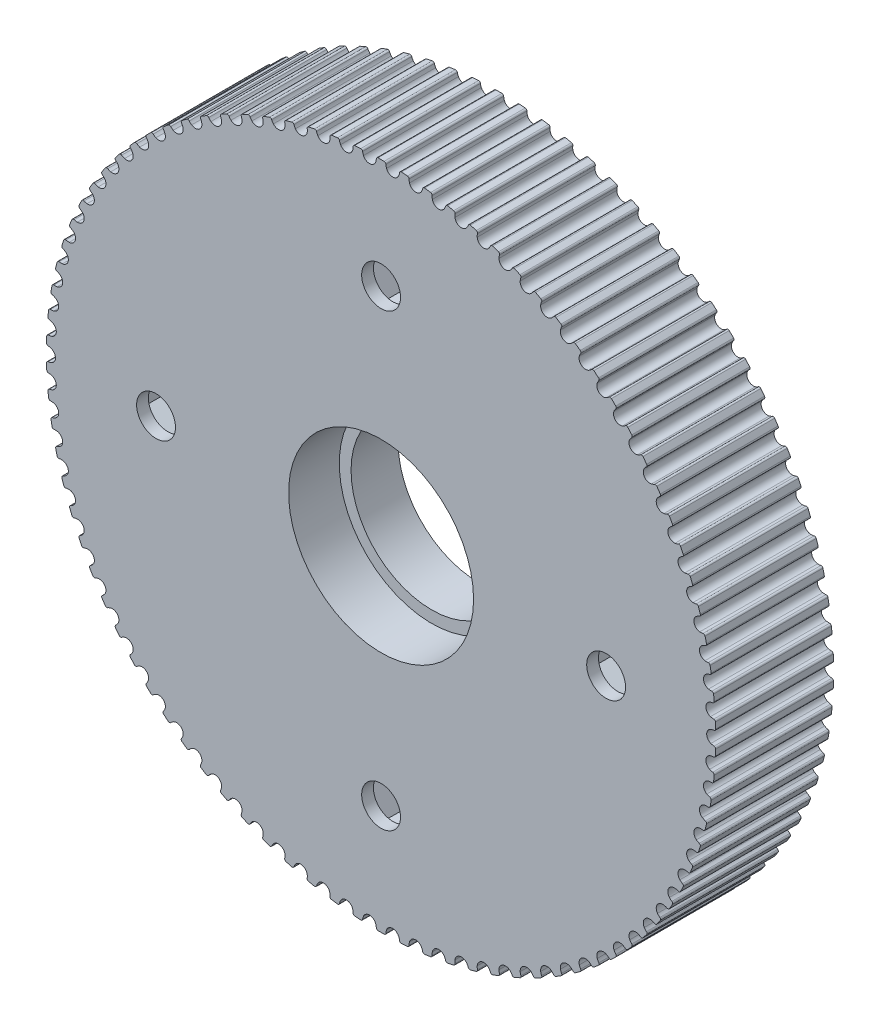
SolidWorks part; units mm, degrees
ref_plane "前视基准面" through (0, 0, 0) normal (0, 0, 1) x (1, 0, 0)
ref_plane "上视基准面" through (0, 0, 0) normal (0, 1, 0) x (1, 0, 0)
ref_plane "右视基准面" through (0, 0, 0) normal (1, 0, 0) x (0, 0, -1)
sketch "草图5" plane through (0, 0, 0) normal (0, 0, 1) x (1, 0, 0)
  line L0 (-10.0057, 26.1448) -> (-10.0057, 26.1386)
  line L1 (-10.0057, -26.1386) -> (-10.0057, -26.1448)
  arc A0 (-8.1576, 26.7791) -> (-8.1799, 27.0557) centre (-9.1558, 26.8376) ccw
  arc A1 (-9.1407, 26.4596) -> (-8.1576, 26.7791) centre (-8.7116, 26.8116) ccw
  arc A2 (-9.2853, 26.6965) -> (-9.1407, 26.4596) centre (-8.3675, 27.0938) ccw
  arc A3 (-9.2853, 26.6965) -> (-9.4729, 26.7784) centre (-9.4229, 26.637) ccw
  arc A4 (-9.4729, 26.7784) -> (-9.9561, 26.6025) centre (-0.0036, 0.01) ccw
  arc A5 (-9.9561, 26.6025) -> (-10.0473, 26.4192) centre (-9.9035, 26.462) ccw
  arc A6 (-10.0057, 26.1448) -> (-10.0473, 26.4192) centre (-11.0056, 26.1336) ccw
  arc A7 (-10.9642, 25.7576) -> (-10.0057, 26.1386) centre (-10.5607, 26.1386) ccw
  arc A8 (-11.1249, 25.9838) -> (-10.9642, 25.7576) centre (-10.2371, 26.4441) ccw
  arc A9 (-11.1249, 25.9838) -> (-11.3178, 26.0523) centre (-11.2581, 25.9148) ccw
  arc A10 (-11.3178, 26.0523) -> (-11.7876, 25.8432) centre (-0.0043, 0.0097) ccw
  arc A11 (-11.7876, 25.8432) -> (-11.8657, 25.654) centre (-11.7253, 25.7067) ccw
  arc A12 (-11.8051, 25.3832) -> (-11.8657, 25.654) centre (-12.8018, 25.3022) ccw
  arc A13 (-11.8033, 25.3382) -> (-11.8051, 25.3832) centre (-12.3583, 25.3382) ccw
  arc A14 (-12.7343, 24.93) -> (-11.8033, 25.3382) centre (-12.3583, 25.3382) ccw
  arc A15 (-12.9103, 25.1445) -> (-12.7343, 24.93) centre (-12.0568, 25.6656) ccw
  arc A16 (-12.9103, 25.1445) -> (-13.1076, 25.1994) centre (-13.0384, 25.0663) ccw
  arc A17 (-13.1076, 25.1994) -> (-13.5616, 24.958) centre (-0.005, 0.0094) ccw
  arc A18 (-13.5616, 24.958) -> (-13.6264, 24.7638) centre (-13.49, 24.8262) ccw
  arc A19 (-13.547, 24.4978) -> (-13.6264, 24.7638) centre (-14.5356, 24.3476) ccw
  arc A20 (-13.5407, 24.4144) -> (-13.547, 24.4978) centre (-14.0957, 24.4144) ccw
  arc A21 (-14.4423, 23.981) -> (-13.5407, 24.4144) centre (-14.0957, 24.4144) ccw
  arc A22 (-14.6329, 24.1827) -> (-14.4423, 23.981) centre (-13.8178, 24.762) ccw
  arc A23 (-14.6329, 24.1827) -> (-14.8335, 24.2237) centre (-14.7551, 24.0957) ccw
  arc A24 (-14.8335, 24.2237) -> (-15.2695, 23.9512) centre (-0.0056, 0.009) ccw
  arc A25 (-15.2695, 23.9512) -> (-15.3206, 23.7529) centre (-15.1889, 23.8247) ccw
  arc A26 (-15.2229, 23.4932) -> (-15.3206, 23.7529) centre (-16.1986, 23.2743) ccw
  arc A27 (-15.2094, 23.3717) -> (-15.2229, 23.4932) centre (-15.7644, 23.3717) ccw
  arc A28 (-16.0799, 22.9151) -> (-15.2094, 23.3717) centre (-15.7644, 23.3717) ccw
  arc A29 (-16.2841, 23.103) -> (-16.0799, 22.9151) centre (-15.5114, 23.7378) ccw
  arc A30 (-16.2841, 23.103) -> (-16.4871, 23.1299) centre (-16.4, 23.0078) ccw
  arc A31 (-16.4871, 23.1299) -> (-16.9031, 22.8277) centre (-0.0063, 0.0086) ccw
  arc A32 (-16.9031, 22.8277) -> (-16.9402, 22.6263) centre (-16.8138, 22.7071) ccw
  arc A33 (-16.8246, 22.3741) -> (-16.9402, 22.6263) centre (-17.7827, 22.0876) ccw
  arc A34 (-16.8013, 22.2151) -> (-16.8246, 22.3741) centre (-17.3563, 22.2151) ccw
  arc A35 (-17.6392, 21.7376) -> (-16.8013, 22.2151) centre (-17.3563, 22.2151) ccw
  arc A36 (-17.856, 21.9108) -> (-17.6392, 21.7376) centre (-17.1295, 22.598) ccw
  arc A37 (-17.856, 21.9108) -> (-18.0604, 21.9235) centre (-17.965, 21.8077) ccw
  arc A38 (-18.0604, 21.9235) -> (-18.4543, 21.593) centre (-0.0068, 0.0082) ccw
  arc A39 (-18.4543, 21.593) -> (-18.4773, 21.3895) centre (-18.3568, 21.479) ccw
  arc A40 (-18.3443, 21.1459) -> (-18.4773, 21.3895) centre (-19.2801, 20.7934) ccw
  arc A41 (-18.3087, 20.9503) -> (-18.3443, 21.1459) centre (-18.8637, 20.9503) ccw
  arc A42 (-19.1126, 20.4542) -> (-18.3087, 20.9503) centre (-18.8637, 20.9503) ccw
  arc A43 (-19.341, 20.6119) -> (-19.1126, 20.4542) centre (-18.6642, 21.348) ccw
  arc A44 (-19.341, 20.6119) -> (-19.5457, 20.6103) centre (-19.4425, 20.5014) ccw
  arc A45 (-19.5457, 20.6103) -> (-19.9156, 20.2531) centre (-0.0074, 0.0077) ccw
  arc A46 (-19.9156, 20.2531) -> (-19.9243, 20.0485) centre (-19.8104, 20.1461) ccw
  arc A47 (-19.7747, 19.8148) -> (-19.9243, 20.0485) centre (-20.6836, 19.3978) ccw
  arc A48 (-19.7242, 19.5834) -> (-19.7747, 19.8148) centre (-20.2792, 19.5834) ccw
  arc A49 (-20.4928, 19.0711) -> (-19.7242, 19.5834) centre (-20.2792, 19.5834) ccw
  arc A50 (-20.7317, 19.2125) -> (-20.4928, 19.0711) centre (-20.1079, 19.9941) ccw
  arc A51 (-20.7317, 19.2125) -> (-20.9358, 19.1966) centre (-20.8252, 19.0953) ccw
  arc A52 (-20.9358, 19.1966) -> (-21.2799, 18.8145) centre (-0.0079, 0.0071) ccw
  arc A53 (-21.2799, 18.8145) -> (-21.2743, 18.6098) centre (-21.1675, 18.7152) ccw
  arc A54 (-21.1088, 18.3871) -> (-21.2743, 18.6098) centre (-21.9864, 17.9077) ccw
  arc A55 (-21.0408, 18.1211) -> (-21.1088, 18.3871) centre (-21.5958, 18.1211) ccw
  arc A56 (-21.7733, 17.5952) -> (-21.0408, 18.1211) centre (-21.5958, 18.1211) ccw
  arc A57 (-22.0214, 17.7195) -> (-21.7733, 17.5952) centre (-21.4536, 18.5427) ccw
  arc A58 (-22.0214, 17.7195) -> (-22.2239, 17.6895) centre (-22.1065, 17.596) ccw
  arc A59 (-22.2239, 17.6895) -> (-22.5405, 17.2843) centre (-0.0084, 0.0066) ccw
  arc A60 (-22.5405, 17.2843) -> (-22.5206, 17.0805) centre (-22.4214, 17.193) ccw
  arc A61 (-22.34, 16.8698) -> (-22.5206, 17.0805) centre (-23.182, 16.3304) ccw
  arc A62 (-22.2523, 16.5705) -> (-22.34, 16.8698) centre (-22.8073, 16.5705) ccw
  arc A63 (-22.9476, 16.0335) -> (-22.2523, 16.5705) centre (-22.8073, 16.5705) ccw
  arc A64 (-23.2038, 16.1402) -> (-22.9476, 16.0335) centre (-22.6948, 17.001) ccw
  arc A65 (-23.2038, 16.1402) -> (-23.4037, 16.0961) centre (-23.2801, 16.0111) ccw
  arc A66 (-23.4037, 16.0961) -> (-23.6912, 15.6698) centre (-0.0088, 0.006) ccw
  arc A67 (-23.6912, 15.6698) -> (-23.6572, 15.4679) centre (-23.5661, 15.5871) ccw
  arc A68 (-23.4623, 15.2704) -> (-23.6572, 15.4679) centre (-24.2647, 14.6736) ccw
  arc A69 (-23.3526, 14.9391) -> (-23.4623, 15.2704) centre (-23.9076, 14.9391) ccw
  arc A70 (-24.0101, 14.3937) -> (-23.3526, 14.9391) centre (-23.9076, 14.9391) ccw
  arc A71 (-24.2731, 14.4823) -> (-24.0101, 14.3937) centre (-23.8254, 15.3765) ccw
  arc A72 (-24.2731, 14.4823) -> (-24.4695, 14.4243) centre (-24.3403, 14.3482) ccw
  arc A73 (-24.4695, 14.4243) -> (-24.7266, 13.979) centre (-0.0092, 0.0053) ccw
  arc A74 (-24.7266, 13.979) -> (-24.6786, 13.78) centre (-24.596, 13.9052) ccw
  arc A75 (-24.4704, 13.5965) -> (-24.6786, 13.78) centre (-25.2292, 12.9452) ccw
  arc A76 (-24.3365, 13.235) -> (-24.4704, 13.5965) centre (-24.8915, 13.235) ccw
  arc A77 (-24.9557, 12.6838) -> (-24.3365, 13.235) centre (-24.8915, 13.235) ccw
  arc A78 (-25.2242, 12.7538) -> (-24.9557, 12.6838) centre (-24.84, 13.6771) ccw
  arc A79 (-25.2242, 12.7538) -> (-25.4161, 12.6823) centre (-25.2819, 12.6153) ccw
  arc A80 (-25.4161, 12.6823) -> (-25.6415, 12.2201) centre (-0.0096, 0.0047) ccw
  arc A81 (-25.6415, 12.2201) -> (-25.5797, 12.0249) centre (-25.5061, 12.1556) ccw
  arc A82 (-25.3592, 11.8565) -> (-25.5797, 12.0249) centre (-26.0707, 11.1538) ccw
  arc A83 (-25.1991, 11.4665) -> (-25.3592, 11.8565) centre (-25.7541, 11.4665) ccw
  arc A84 (-25.7797, 10.9121) -> (-25.1991, 11.4665) centre (-25.7541, 11.4665) ccw
  arc A85 (-26.0524, 10.9632) -> (-25.7797, 10.9121) centre (-25.7336, 11.911) ccw
  arc A86 (-26.0524, 10.9632) -> (-26.2388, 10.8785) centre (-26.1003, 10.821) ccw
  arc A87 (-26.2388, 10.8785) -> (-26.4315, 10.4017) centre (-0.0099, 0.004) ccw
  arc A88 (-26.4315, 10.4017) -> (-26.3562, 10.2113) centre (-26.2919, 10.3468) ccw
  arc A89 (-26.1245, 10.0586) -> (-26.3562, 10.2113) centre (-26.7853, 9.308) ccw
  arc A90 (-25.9362, 9.642) -> (-26.1245, 10.0586) centre (-26.4912, 9.642) ccw
  arc A91 (-26.4781, 9.0872) -> (-25.9362, 9.642) centre (-26.4912, 9.642) ccw
  arc A92 (-26.7537, 9.1192) -> (-26.4781, 9.0872) centre (-26.5018, 10.0869) ccw
  arc A93 (-26.7537, 9.1192) -> (-26.9338, 9.0216) centre (-26.7915, 8.974) ccw
  arc A94 (-26.9338, 9.0216) -> (-27.0927, 8.5326) centre (-0.0101, 0.0033) ccw
  arc A95 (-27.0927, 8.5326) -> (-27.0043, 8.3479) centre (-26.9496, 8.4876) ccw
  arc A96 (-26.7625, 8.2117) -> (-27.0043, 8.3479) centre (-27.3693, 7.4169) ccw
  arc A97 (-26.5443, 7.7706) -> (-26.7625, 8.2117) centre (-27.0993, 7.7706) ccw
  arc A98 (-27.0475, 7.218) -> (-26.5443, 7.7706) centre (-27.0993, 7.7706) ccw
  arc A99 (-27.3247, 7.2307) -> (-27.0475, 7.218) centre (-27.1408, 8.2137) ccw
  arc A100 (-27.3247, 7.2307) -> (-27.4975, 7.1209) centre (-27.3523, 7.0833) ccw
  arc A101 (-27.4975, 7.1209) -> (-27.6219, 6.6219) centre (-0.0103, 0.0026) ccw
  arc A102 (-27.6219, 6.6219) -> (-27.5209, 6.4438) centre (-27.476, 6.587) ccw
  arc A103 (-27.2702, 6.3249) -> (-27.5209, 6.4438) centre (-27.82, 5.4896) ccw
  arc A104 (-27.0203, 5.8613) -> (-27.2702, 6.3249) centre (-27.5753, 5.8613) ccw
  arc A105 (-27.4851, 5.3137) -> (-27.0203, 5.8613) centre (-27.5753, 5.8613) ccw
  arc A106 (-27.7625, 5.307) -> (-27.4851, 5.3137) centre (-27.6477, 6.3004) ccw
  arc A107 (-27.7625, 5.307) -> (-27.9272, 5.1854) centre (-27.7797, 5.158) ccw
  arc A108 (-27.9272, 5.1854) -> (-28.0165, 4.679) centre (-0.0105, 0.0018) ccw
  arc A109 (-28.0165, 4.679) -> (-27.9033, 4.5084) centre (-27.8686, 4.6543) ccw
  arc A110 (-27.6449, 4.4072) -> (-27.9033, 4.5084) centre (-28.1352, 3.5356) ccw
  arc A111 (-27.362, 3.9235) -> (-27.6449, 4.4072) centre (-27.917, 3.9235) ccw
  arc A112 (-27.7888, 3.3835) -> (-27.362, 3.9235) centre (-27.917, 3.9235) ccw
  arc A113 (-28.0651, 3.3575) -> (-27.7888, 3.3835) centre (-28.0198, 4.3564) ccw
  arc A114 (-28.0651, 3.3575) -> (-28.2209, 3.2247) centre (-28.0719, 3.2076) ccw
  arc A115 (-28.2209, 3.2247) -> (-28.2747, 2.7133) centre (-0.0106, 0.0011) ccw
  arc A116 (-28.2747, 2.7133) -> (-28.1499, 2.551) centre (-28.1253, 2.6989) ccw
  arc A117 (-27.885, 2.4681) -> (-28.1499, 2.551) centre (-28.3133, 1.5644) ccw
  arc A118 (-27.5677, 1.9665) -> (-27.885, 2.4681) centre (-28.1227, 1.9665) ccw
  arc A119 (-27.9571, 1.4368) -> (-27.5677, 1.9665) centre (-28.1227, 1.9665) ccw
  arc A120 (-28.2309, 1.3916) -> (-27.9571, 1.4368) centre (-28.2554, 2.3913) ccw
  arc A121 (-28.2309, 1.3916) -> (-28.3771, 1.2482) centre (-28.2272, 1.2416) ccw
  arc A122 (-28.3771, 1.2482) -> (-28.395, 0.7343) centre (-0.0106, 0.0004) ccw
  arc A123 (-28.395, 0.7343) -> (-28.2592, 0.5811) centre (-28.2451, 0.7304) ccw
  arc A124 (-27.9893, 0.5169) -> (-28.2592, 0.5811) centre (-28.3534, -0.4144) ccw
  arc A125 (-27.6364, 0) -> (-27.9893, 0.5169) centre (-28.1914, 0) ccw
  arc A126 (-27.9893, -0.5169) -> (-27.6364, 0) centre (-28.1914, 0) ccw
  arc A127 (-28.2592, -0.5811) -> (-27.9893, -0.5169) centre (-28.3534, 0.4144) ccw
  arc A128 (-28.2592, -0.5811) -> (-28.395, -0.7343) centre (-28.2451, -0.7304) ccw
  arc A129 (-28.395, -0.7343) -> (-28.3771, -1.2482) centre (-0.0106, -0.0004) ccw
  arc A130 (-28.3771, -1.2482) -> (-28.2309, -1.3916) centre (-28.2272, -1.2416) ccw
  arc A131 (-27.9571, -1.4368) -> (-28.2309, -1.3916) centre (-28.2554, -2.3913) ccw
  arc A132 (-27.5677, -1.9665) -> (-27.9571, -1.4368) centre (-28.1227, -1.9665) ccw
  arc A133 (-27.885, -2.4681) -> (-27.5677, -1.9665) centre (-28.1227, -1.9665) ccw
  arc A134 (-28.1499, -2.551) -> (-27.885, -2.4681) centre (-28.3133, -1.5644) ccw
  arc A135 (-28.1499, -2.551) -> (-28.2747, -2.7133) centre (-28.1253, -2.6989) ccw
  arc A136 (-28.2747, -2.7133) -> (-28.2209, -3.2247) centre (-0.0106, -0.0011) ccw
  arc A137 (-28.2209, -3.2247) -> (-28.0651, -3.3575) centre (-28.0719, -3.2076) ccw
  arc A138 (-27.7888, -3.3835) -> (-28.0651, -3.3575) centre (-28.0198, -4.3564) ccw
  arc A139 (-27.362, -3.9235) -> (-27.7888, -3.3835) centre (-27.917, -3.9235) ccw
  arc A140 (-27.6449, -4.4072) -> (-27.362, -3.9235) centre (-27.917, -3.9235) ccw
  arc A141 (-27.9033, -4.5084) -> (-27.6449, -4.4072) centre (-28.1352, -3.5356) ccw
  arc A142 (-27.9033, -4.5084) -> (-28.0165, -4.679) centre (-27.8686, -4.6543) ccw
  arc A143 (-28.0165, -4.679) -> (-27.9272, -5.1854) centre (-0.0105, -0.0018) ccw
  arc A144 (-27.9272, -5.1854) -> (-27.7625, -5.307) centre (-27.7797, -5.158) ccw
  arc A145 (-27.4851, -5.3137) -> (-27.7625, -5.307) centre (-27.6477, -6.3004) ccw
  arc A146 (-27.0203, -5.8613) -> (-27.4851, -5.3137) centre (-27.5753, -5.8613) ccw
  arc A147 (-27.2702, -6.3249) -> (-27.0203, -5.8613) centre (-27.5753, -5.8613) ccw
  arc A148 (-27.5209, -6.4438) -> (-27.2702, -6.3249) centre (-27.82, -5.4896) ccw
  arc A149 (-27.5209, -6.4438) -> (-27.6219, -6.6219) centre (-27.476, -6.587) ccw
  arc A150 (-27.6219, -6.6219) -> (-27.4975, -7.1209) centre (-0.0103, -0.0026) ccw
  arc A151 (-27.4975, -7.1209) -> (-27.3247, -7.2307) centre (-27.3523, -7.0833) ccw
  arc A152 (-27.0475, -7.218) -> (-27.3247, -7.2307) centre (-27.1408, -8.2137) ccw
  arc A153 (-26.5443, -7.7706) -> (-27.0475, -7.218) centre (-27.0993, -7.7706) ccw
  arc A154 (-26.7625, -8.2117) -> (-26.5443, -7.7706) centre (-27.0993, -7.7706) ccw
  arc A155 (-27.0043, -8.3479) -> (-26.7625, -8.2117) centre (-27.3693, -7.4169) ccw
  arc A156 (-27.0043, -8.3479) -> (-27.0927, -8.5326) centre (-26.9496, -8.4876) ccw
  arc A157 (-27.0927, -8.5326) -> (-26.9338, -9.0216) centre (-0.0101, -0.0033) ccw
  arc A158 (-26.9338, -9.0216) -> (-26.7537, -9.1192) centre (-26.7915, -8.974) ccw
  arc A159 (-26.4781, -9.0872) -> (-26.7537, -9.1192) centre (-26.5018, -10.0869) ccw
  arc A160 (-25.9362, -9.642) -> (-26.4781, -9.0872) centre (-26.4912, -9.642) ccw
  arc A161 (-26.1245, -10.0586) -> (-25.9362, -9.642) centre (-26.4912, -9.642) ccw
  arc A162 (-26.3562, -10.2113) -> (-26.1245, -10.0586) centre (-26.7853, -9.308) ccw
  arc A163 (-26.3562, -10.2113) -> (-26.4315, -10.4017) centre (-26.2919, -10.3468) ccw
  arc A164 (-26.4315, -10.4017) -> (-26.2388, -10.8785) centre (-0.0099, -0.004) ccw
  arc A165 (-26.2388, -10.8785) -> (-26.0524, -10.9632) centre (-26.1003, -10.821) ccw
  arc A166 (-25.7797, -10.9121) -> (-26.0524, -10.9632) centre (-25.7336, -11.911) ccw
  arc A167 (-25.1991, -11.4665) -> (-25.7797, -10.9121) centre (-25.7541, -11.4665) ccw
  arc A168 (-25.3592, -11.8565) -> (-25.1991, -11.4665) centre (-25.7541, -11.4665) ccw
  arc A169 (-25.5797, -12.0249) -> (-25.3592, -11.8565) centre (-26.0707, -11.1538) ccw
  arc A170 (-25.5797, -12.0249) -> (-25.6415, -12.2201) centre (-25.5061, -12.1556) ccw
  arc A171 (-25.6415, -12.2201) -> (-25.4161, -12.6823) centre (-0.0096, -0.0047) ccw
  arc A172 (-25.4161, -12.6823) -> (-25.2242, -12.7538) centre (-25.2819, -12.6153) ccw
  arc A173 (-24.9557, -12.6838) -> (-25.2242, -12.7538) centre (-24.84, -13.6771) ccw
  arc A174 (-24.3365, -13.235) -> (-24.9557, -12.6838) centre (-24.8915, -13.235) ccw
  arc A175 (-24.4704, -13.5965) -> (-24.3365, -13.235) centre (-24.8915, -13.235) ccw
  arc A176 (-24.6786, -13.78) -> (-24.4704, -13.5965) centre (-25.2292, -12.9452) ccw
  arc A177 (-24.6786, -13.78) -> (-24.7266, -13.979) centre (-24.596, -13.9052) ccw
  arc A178 (-24.7266, -13.979) -> (-24.4695, -14.4243) centre (-0.0092, -0.0053) ccw
  arc A179 (-24.4695, -14.4243) -> (-24.2731, -14.4823) centre (-24.3403, -14.3482) ccw
  arc A180 (-24.0101, -14.3937) -> (-24.2731, -14.4823) centre (-23.8254, -15.3765) ccw
  arc A181 (-23.3526, -14.9391) -> (-24.0101, -14.3937) centre (-23.9076, -14.9391) ccw
  arc A182 (-23.4623, -15.2704) -> (-23.3526, -14.9391) centre (-23.9076, -14.9391) ccw
  arc A183 (-23.6572, -15.4679) -> (-23.4623, -15.2704) centre (-24.2647, -14.6736) ccw
  arc A184 (-23.6572, -15.4679) -> (-23.6912, -15.6698) centre (-23.5661, -15.5871) ccw
  arc A185 (-23.6912, -15.6698) -> (-23.4037, -16.0961) centre (-0.0088, -0.006) ccw
  arc A186 (-23.4037, -16.0961) -> (-23.2038, -16.1402) centre (-23.2801, -16.0111) ccw
  arc A187 (-22.9476, -16.0335) -> (-23.2038, -16.1402) centre (-22.6948, -17.001) ccw
  arc A188 (-22.2523, -16.5705) -> (-22.9476, -16.0335) centre (-22.8073, -16.5705) ccw
  arc A189 (-22.34, -16.8698) -> (-22.2523, -16.5705) centre (-22.8073, -16.5705) ccw
  arc A190 (-22.5206, -17.0805) -> (-22.34, -16.8698) centre (-23.182, -16.3304) ccw
  arc A191 (-22.5206, -17.0805) -> (-22.5405, -17.2843) centre (-22.4214, -17.193) ccw
  arc A192 (-22.5405, -17.2843) -> (-22.2239, -17.6895) centre (-0.0084, -0.0066) ccw
  arc A193 (-22.2239, -17.6895) -> (-22.0214, -17.7195) centre (-22.1065, -17.596) ccw
  arc A194 (-21.7733, -17.5952) -> (-22.0214, -17.7195) centre (-21.4536, -18.5427) ccw
  arc A195 (-21.0408, -18.1211) -> (-21.7733, -17.5952) centre (-21.5958, -18.1211) ccw
  arc A196 (-21.1088, -18.3871) -> (-21.0408, -18.1211) centre (-21.5958, -18.1211) ccw
  arc A197 (-21.2743, -18.6098) -> (-21.1088, -18.3871) centre (-21.9864, -17.9077) ccw
  arc A198 (-21.2743, -18.6098) -> (-21.2799, -18.8145) centre (-21.1675, -18.7152) ccw
  arc A199 (-21.2799, -18.8145) -> (-20.9358, -19.1966) centre (-0.0079, -0.0071) ccw
  arc A200 (-20.9358, -19.1966) -> (-20.7317, -19.2125) centre (-20.8252, -19.0953) ccw
  arc A201 (-20.4928, -19.0711) -> (-20.7317, -19.2125) centre (-20.1079, -19.9941) ccw
  arc A202 (-19.7242, -19.5834) -> (-20.4928, -19.0711) centre (-20.2792, -19.5834) ccw
  arc A203 (-19.7747, -19.8148) -> (-19.7242, -19.5834) centre (-20.2792, -19.5834) ccw
  arc A204 (-19.9243, -20.0485) -> (-19.7747, -19.8148) centre (-20.6836, -19.3978) ccw
  arc A205 (-19.9243, -20.0485) -> (-19.9156, -20.2531) centre (-19.8104, -20.1461) ccw
  arc A206 (-19.9156, -20.2531) -> (-19.5457, -20.6103) centre (-0.0074, -0.0077) ccw
  arc A207 (-19.5457, -20.6103) -> (-19.341, -20.6119) centre (-19.4425, -20.5014) ccw
  arc A208 (-19.1126, -20.4542) -> (-19.341, -20.6119) centre (-18.6642, -21.348) ccw
  arc A209 (-18.3087, -20.9503) -> (-19.1126, -20.4542) centre (-18.8637, -20.9503) ccw
  arc A210 (-18.3443, -21.1459) -> (-18.3087, -20.9503) centre (-18.8637, -20.9503) ccw
  arc A211 (-18.4773, -21.3895) -> (-18.3443, -21.1459) centre (-19.2801, -20.7934) ccw
  arc A212 (-18.4773, -21.3895) -> (-18.4543, -21.593) centre (-18.3568, -21.479) ccw
  arc A213 (-18.4543, -21.593) -> (-18.0604, -21.9235) centre (-0.0068, -0.0082) ccw
  arc A214 (-18.0604, -21.9235) -> (-17.856, -21.9108) centre (-17.965, -21.8077) ccw
  arc A215 (-17.6392, -21.7376) -> (-17.856, -21.9108) centre (-17.1295, -22.598) ccw
  arc A216 (-16.8013, -22.2151) -> (-17.6392, -21.7376) centre (-17.3563, -22.2151) ccw
  arc A217 (-16.8246, -22.3741) -> (-16.8013, -22.2151) centre (-17.3563, -22.2151) ccw
  arc A218 (-16.9402, -22.6263) -> (-16.8246, -22.3741) centre (-17.7827, -22.0876) ccw
  arc A219 (-16.9402, -22.6263) -> (-16.9031, -22.8277) centre (-16.8138, -22.7071) ccw
  arc A220 (-16.9031, -22.8277) -> (-16.4871, -23.1299) centre (-0.0063, -0.0086) ccw
  arc A221 (-16.4871, -23.1299) -> (-16.2841, -23.103) centre (-16.4, -23.0078) ccw
  arc A222 (-16.0799, -22.9151) -> (-16.2841, -23.103) centre (-15.5114, -23.7378) ccw
  arc A223 (-15.2094, -23.3717) -> (-16.0799, -22.9151) centre (-15.7644, -23.3717) ccw
  arc A224 (-15.2229, -23.4932) -> (-15.2094, -23.3717) centre (-15.7644, -23.3717) ccw
  arc A225 (-15.3206, -23.7529) -> (-15.2229, -23.4932) centre (-16.1986, -23.2743) ccw
  arc A226 (-15.3206, -23.7529) -> (-15.2695, -23.9512) centre (-15.1889, -23.8247) ccw
  arc A227 (-15.2695, -23.9512) -> (-14.8335, -24.2237) centre (-0.0056, -0.009) ccw
  arc A228 (-14.8335, -24.2237) -> (-14.6329, -24.1827) centre (-14.7551, -24.0957) ccw
  arc A229 (-14.4423, -23.981) -> (-14.6329, -24.1827) centre (-13.8178, -24.762) ccw
  arc A230 (-13.5407, -24.4144) -> (-14.4423, -23.981) centre (-14.0957, -24.4144) ccw
  arc A231 (-13.547, -24.4978) -> (-13.5407, -24.4144) centre (-14.0957, -24.4144) ccw
  arc A232 (-13.6264, -24.7638) -> (-13.547, -24.4978) centre (-14.5356, -24.3476) ccw
  arc A233 (-13.6264, -24.7638) -> (-13.5616, -24.958) centre (-13.49, -24.8262) ccw
  arc A234 (-13.5616, -24.958) -> (-13.1076, -25.1994) centre (-0.005, -0.0094) ccw
  arc A235 (-13.1076, -25.1994) -> (-12.9103, -25.1445) centre (-13.0384, -25.0663) ccw
  arc A236 (-12.7343, -24.93) -> (-12.9103, -25.1445) centre (-12.0568, -25.6656) ccw
  arc A237 (-11.8033, -25.3382) -> (-12.7343, -24.93) centre (-12.3583, -25.3382) ccw
  arc A238 (-11.8051, -25.3832) -> (-11.8033, -25.3382) centre (-12.3583, -25.3382) ccw
  arc A239 (-11.8657, -25.654) -> (-11.8051, -25.3832) centre (-12.8018, -25.3022) ccw
  arc A240 (-11.8657, -25.654) -> (-11.7876, -25.8432) centre (-11.7253, -25.7067) ccw
  arc A241 (-11.7876, -25.8432) -> (-11.3178, -26.0523) centre (-0.0043, -0.0097) ccw
  arc A242 (-11.3178, -26.0523) -> (-11.1249, -25.9838) centre (-11.2581, -25.9148) ccw
  arc A243 (-10.9642, -25.7576) -> (-11.1249, -25.9838) centre (-10.2371, -26.4441) ccw
  arc A244 (-10.0057, -26.1386) -> (-10.9642, -25.7576) centre (-10.5607, -26.1386) ccw
  arc A245 (-10.0473, -26.4192) -> (-10.0057, -26.1448) centre (-11.0056, -26.1336) ccw
  arc A246 (-10.0473, -26.4192) -> (-9.9561, -26.6025) centre (-9.9035, -26.462) ccw
  arc A247 (-9.9561, -26.6025) -> (-9.4729, -26.7784) centre (-0.0036, -0.01) ccw
  arc A248 (-9.4729, -26.7784) -> (-9.2853, -26.6965) centre (-9.4229, -26.637) ccw
  arc A249 (-9.1407, -26.4596) -> (-9.2853, -26.6965) centre (-8.3675, -27.0938) ccw
  arc A250 (-8.1576, -26.7791) -> (-9.1407, -26.4596) centre (-8.7116, -26.8116) ccw
  arc A251 (-8.1799, -27.0557) -> (-8.1576, -26.7791) centre (-9.1558, -26.8376) ccw
  arc A252 (-8.1799, -27.0557) -> (-8.0762, -27.2322) centre (-8.0335, -27.0884) ccw
  arc A253 (-8.0762, -27.2322) -> (-7.5819, -27.3739) centre (-0.0029, -0.0102) ccw
  arc A254 (-7.5819, -27.3739) -> (-7.4004, -27.2792) centre (-7.5419, -27.2294) ccw
  arc A255 (-7.2727, -27.0328) -> (-7.4004, -27.2792) centre (-6.4572, -27.6115) ccw
  arc A256 (-6.2697, -27.2829) -> (-7.2727, -27.0328) centre (-6.8201, -27.354) ccw
  arc A257 (-6.2727, -27.5604) -> (-6.2697, -27.2829) centre (-7.2614, -27.4109) ccw
  arc A258 (-6.2727, -27.5604) -> (-6.1569, -27.7292) centre (-6.1244, -27.5828) ccw
  arc A259 (-6.1569, -27.7292) -> (-5.6539, -27.8361) centre (-0.0022, -0.0104) ccw
  arc A260 (-5.6539, -27.8361) -> (-5.4794, -27.729) centre (-5.6241, -27.6892) ccw
  arc A261 (-5.3693, -27.4743) -> (-5.4794, -27.729) centre (-4.5154, -27.9946) ccw
  arc A262 (-4.3512, -27.6538) -> (-5.3693, -27.4743) centre (-4.8954, -27.7631) ccw
  arc A263 (-4.3349, -27.9308) -> (-4.3512, -27.6538) centre (-5.3317, -27.8507) ccw
  arc A264 (-4.3349, -27.9308) -> (-4.2076, -28.0912) centre (-4.1854, -27.9428) ccw
  arc A265 (-4.2076, -28.0912) -> (-3.6984, -28.1627) centre (-0.0015, -0.0105) ccw
  arc A266 (-3.6984, -28.1627) -> (-3.5318, -28.0437) centre (-3.6789, -28.014) ccw
  arc A267 (-3.4397, -27.7819) -> (-3.5318, -28.0437) centre (-2.5516, -28.2414) ccw
  arc A268 (-2.4116, -27.89) -> (-3.4397, -27.7819) centre (-2.9468, -28.0369) ccw
  arc A269 (-2.376, -28.1652) -> (-2.4116, -27.89) centre (-3.3759, -28.1548) ccw
  arc A270 (-2.376, -28.1652) -> (-2.2378, -28.3163) centre (-2.226, -28.1667) ccw
  arc A271 (-2.2378, -28.3163) -> (-1.7248, -28.3521) centre (-0.0007, -0.0106) ccw
  arc A272 (-1.7248, -28.3521) -> (-1.567, -28.2217) centre (-1.7157, -28.2024) ccw
  arc A273 (-1.4934, -27.9542) -> (-1.567, -28.2217) centre (-0.5753, -28.3506) ccw
  arc A274 (-0.4602, -27.9902) -> (-1.4934, -27.9542) centre (-0.9839, -28.1742) ccw
  arc A275 (-0.4055, -28.2623) -> (-0.4602, -27.9902) centre (-1.4037, -28.3217) ccw
  arc A276 (-0.4055, -28.2623) -> (-0.2571, -28.4034) centre (-0.2557, -28.2534) ccw
  arc A277 (-0.2571, -28.4034) -> (0.2571, -28.4034) centre (0, -0.0107) ccw
  arc A278 (0.2571, -28.4034) -> (0.4055, -28.2623) centre (0.2557, -28.2534) ccw
  arc A279 (0.4602, -27.9902) -> (0.4055, -28.2623) centre (1.4037, -28.3217) ccw
  arc A280 (1.4934, -27.9542) -> (0.4602, -27.9902) centre (0.9839, -28.1742) ccw
  arc A281 (1.567, -28.2217) -> (1.4934, -27.9542) centre (0.5753, -28.3506) ccw
  arc A282 (1.567, -28.2217) -> (1.7248, -28.3521) centre (1.7157, -28.2024) ccw
  arc A283 (1.7248, -28.3521) -> (2.2378, -28.3163) centre (0.0007, -0.0106) ccw
  arc A284 (2.2378, -28.3163) -> (2.376, -28.1652) centre (2.226, -28.1667) ccw
  arc A285 (2.3759, -28.1548) -> (2.376, -28.1652) centre (3.3759, -28.1548) ccw
  arc A286 (2.4116, -27.89) -> (2.3759, -28.1548) centre (3.3759, -28.1548) ccw
  arc A287 (3.4397, -27.7819) -> (2.4116, -27.89) centre (2.9468, -28.0369) ccw
  arc A288 (3.5318, -28.0437) -> (3.4397, -27.7819) centre (2.5516, -28.2414) ccw
  arc A289 (3.5318, -28.0437) -> (3.6984, -28.1627) centre (3.6789, -28.014) ccw
  arc A290 (3.6984, -28.1627) -> (4.2076, -28.0912) centre (0.0015, -0.0105) ccw
  arc A291 (4.2076, -28.0912) -> (4.3354, -27.9428) centre (4.1854, -27.9428) ccw
  arc A292 (4.3354, -27.9428) -> (4.3349, -27.9308) centre (4.1854, -27.9428) ccw
  arc A293 (4.3317, -27.8507) -> (4.3349, -27.9308) centre (5.3317, -27.8507) ccw
  arc A294 (4.3512, -27.6538) -> (4.3317, -27.8507) centre (5.3317, -27.8507) ccw
  arc A295 (5.3693, -27.4743) -> (4.3512, -27.6538) centre (4.8954, -27.7631) ccw
  arc A296 (5.4794, -27.729) -> (5.3693, -27.4743) centre (4.5154, -27.9946) ccw
  arc A297 (5.4794, -27.729) -> (5.6539, -27.8361) centre (5.6241, -27.6892) ccw
  arc A298 (5.6539, -27.8361) -> (6.1569, -27.7292) centre (0.0022, -0.0104) ccw
  arc A299 (6.1569, -27.7292) -> (6.2744, -27.5828) centre (6.1244, -27.5828) ccw
  arc A300 (6.2744, -27.5828) -> (6.2727, -27.5604) centre (6.1244, -27.5828) ccw
  arc A301 (6.2614, -27.4109) -> (6.2727, -27.5604) centre (7.2614, -27.4109) ccw
  arc A302 (6.2697, -27.2829) -> (6.2614, -27.4109) centre (7.2614, -27.4109) ccw
  arc A303 (7.2727, -27.0328) -> (6.2697, -27.2829) centre (6.8201, -27.354) ccw
  arc A304 (7.4004, -27.2792) -> (7.2727, -27.0328) centre (6.4572, -27.6115) ccw
  arc A305 (7.4004, -27.2792) -> (7.5819, -27.3739) centre (7.5419, -27.2294) ccw
  arc A306 (7.5819, -27.3739) -> (8.0762, -27.2322) centre (0.0029, -0.0102) ccw
  arc A307 (8.0762, -27.2322) -> (8.1835, -27.0884) centre (8.0335, -27.0884) ccw
  arc A308 (8.1835, -27.0884) -> (8.1799, -27.0557) centre (8.0335, -27.0884) ccw
  arc A309 (8.1558, -26.8376) -> (8.1799, -27.0557) centre (9.1558, -26.8376) ccw
  arc A310 (8.1576, -26.7791) -> (8.1558, -26.8376) centre (9.1558, -26.8376) ccw
  arc A311 (9.1407, -26.4596) -> (8.1576, -26.7791) centre (8.7116, -26.8116) ccw
  arc A312 (9.2853, -26.6965) -> (9.1407, -26.4596) centre (8.3675, -27.0938) ccw
  arc A313 (9.2853, -26.6965) -> (9.4729, -26.7784) centre (9.4229, -26.637) ccw
  arc A314 (9.4729, -26.7784) -> (9.9561, -26.6025) centre (0.0036, -0.01) ccw
  arc A315 (9.9561, -26.6025) -> (10.0535, -26.462) centre (9.9035, -26.462) ccw
  arc A316 (10.0535, -26.462) -> (10.0473, -26.4192) centre (9.9035, -26.462) ccw
  arc A317 (10.0057, -26.1448) -> (10.0473, -26.4192) centre (11.0056, -26.1336) ccw
  arc A318 (10.9642, -25.7576) -> (10.0057, -26.1448) centre (10.5607, -26.1386) ccw
  arc A319 (11.1249, -25.9838) -> (10.9642, -25.7576) centre (10.2371, -26.4441) ccw
  arc A320 (11.1249, -25.9838) -> (11.3178, -26.0523) centre (11.2581, -25.9148) ccw
  arc A321 (11.3178, -26.0523) -> (11.7876, -25.8432) centre (0.0043, -0.0097) ccw
  arc A322 (11.7876, -25.8432) -> (11.8753, -25.7067) centre (11.7253, -25.7067) ccw
  arc A323 (11.8753, -25.7067) -> (11.8657, -25.654) centre (11.7253, -25.7067) ccw
  arc A324 (11.8051, -25.3832) -> (11.8657, -25.654) centre (12.8018, -25.3022) ccw
  arc A325 (12.7343, -24.93) -> (11.8051, -25.3832) centre (12.3583, -25.3382) ccw
  arc A326 (12.9103, -25.1445) -> (12.7343, -24.93) centre (12.0568, -25.6656) ccw
  arc A327 (12.9103, -25.1445) -> (13.1076, -25.1994) centre (13.0384, -25.0663) ccw
  arc A328 (13.1076, -25.1994) -> (13.5616, -24.958) centre (0.005, -0.0094) ccw
  arc A329 (13.5616, -24.958) -> (13.64, -24.8262) centre (13.49, -24.8262) ccw
  arc A330 (13.64, -24.8262) -> (13.6264, -24.7638) centre (13.49, -24.8262) ccw
  arc A331 (13.547, -24.4978) -> (13.6264, -24.7638) centre (14.5356, -24.3476) ccw
  arc A332 (14.4423, -23.981) -> (13.547, -24.4978) centre (14.0957, -24.4144) ccw
  arc A333 (14.6329, -24.1827) -> (14.4423, -23.981) centre (13.8178, -24.762) ccw
  arc A334 (14.6329, -24.1827) -> (14.8335, -24.2237) centre (14.7551, -24.0957) ccw
  arc A335 (14.8335, -24.2237) -> (15.2695, -23.9512) centre (0.0056, -0.009) ccw
  arc A336 (15.2695, -23.9512) -> (15.3389, -23.8247) centre (15.1889, -23.8247) ccw
  arc A337 (15.3389, -23.8247) -> (15.3206, -23.7529) centre (15.1889, -23.8247) ccw
  arc A338 (15.2229, -23.4932) -> (15.3206, -23.7529) centre (16.1986, -23.2743) ccw
  arc A339 (16.0799, -22.9151) -> (15.2229, -23.4932) centre (15.7644, -23.3717) ccw
  arc A340 (16.2841, -23.103) -> (16.0799, -22.9151) centre (15.5114, -23.7378) ccw
  arc A341 (16.2841, -23.103) -> (16.4871, -23.1299) centre (16.4, -23.0078) ccw
  arc A342 (16.4871, -23.1299) -> (16.9031, -22.8277) centre (0.0063, -0.0086) ccw
  arc A343 (16.9031, -22.8277) -> (16.9638, -22.7071) centre (16.8138, -22.7071) ccw
  arc A344 (16.9638, -22.7071) -> (16.9402, -22.6263) centre (16.8138, -22.7071) ccw
  arc A345 (16.8246, -22.3741) -> (16.9402, -22.6263) centre (17.7827, -22.0876) ccw
  arc A346 (17.6392, -21.7376) -> (16.8246, -22.3741) centre (17.3563, -22.2151) ccw
  arc A347 (17.856, -21.9108) -> (17.6392, -21.7376) centre (17.1295, -22.598) ccw
  arc A348 (17.856, -21.9108) -> (18.0604, -21.9235) centre (17.965, -21.8077) ccw
  arc A349 (18.0604, -21.9235) -> (18.4543, -21.593) centre (0.0068, -0.0082) ccw
  arc A350 (18.4543, -21.593) -> (18.5068, -21.479) centre (18.3568, -21.479) ccw
  arc A351 (18.5068, -21.479) -> (18.4773, -21.3895) centre (18.3568, -21.479) ccw
  arc A352 (18.3443, -21.1459) -> (18.4773, -21.3895) centre (19.2801, -20.7934) ccw
  arc A353 (19.1126, -20.4542) -> (18.3443, -21.1459) centre (18.8637, -20.9503) ccw
  arc A354 (19.341, -20.6119) -> (19.1126, -20.4542) centre (18.6642, -21.348) ccw
  arc A355 (19.341, -20.6119) -> (19.5457, -20.6103) centre (19.4425, -20.5014) ccw
  arc A356 (19.5457, -20.6103) -> (19.9156, -20.2531) centre (0.0074, -0.0077) ccw
  arc A357 (19.9156, -20.2531) -> (19.9604, -20.1461) centre (19.8104, -20.1461) ccw
  arc A358 (19.9604, -20.1461) -> (19.9243, -20.0485) centre (19.8104, -20.1461) ccw
  arc A359 (19.7747, -19.8148) -> (19.9243, -20.0485) centre (20.6836, -19.3978) ccw
  arc A360 (20.4928, -19.0711) -> (19.7747, -19.8148) centre (20.2792, -19.5834) ccw
  arc A361 (20.7317, -19.2125) -> (20.4928, -19.0711) centre (20.1079, -19.9941) ccw
  arc A362 (20.7317, -19.2125) -> (20.9358, -19.1966) centre (20.8252, -19.0953) ccw
  arc A363 (20.9358, -19.1966) -> (21.2799, -18.8145) centre (0.0079, -0.0071) ccw
  arc A364 (21.2799, -18.8145) -> (21.3175, -18.7152) centre (21.1675, -18.7152) ccw
  arc A365 (21.3175, -18.7152) -> (21.2743, -18.6098) centre (21.1675, -18.7152) ccw
  arc A366 (21.1088, -18.3871) -> (21.2743, -18.6098) centre (21.9864, -17.9077) ccw
  arc A367 (21.7733, -17.5952) -> (21.1088, -18.3871) centre (21.5958, -18.1211) ccw
  arc A368 (22.0214, -17.7195) -> (21.7733, -17.5952) centre (21.4536, -18.5427) ccw
  arc A369 (22.0214, -17.7195) -> (22.2239, -17.6895) centre (22.1065, -17.596) ccw
  arc A370 (22.2239, -17.6895) -> (22.5405, -17.2843) centre (0.0084, -0.0066) ccw
  arc A371 (22.5405, -17.2843) -> (22.5714, -17.193) centre (22.4214, -17.193) ccw
  arc A372 (22.5714, -17.193) -> (22.5206, -17.0805) centre (22.4214, -17.193) ccw
  arc A373 (22.34, -16.8698) -> (22.5206, -17.0805) centre (23.182, -16.3304) ccw
  arc A374 (22.9476, -16.0335) -> (22.34, -16.8698) centre (22.8073, -16.5705) ccw
  arc A375 (23.2038, -16.1402) -> (22.9476, -16.0335) centre (22.6948, -17.001) ccw
  arc A376 (23.2038, -16.1402) -> (23.4037, -16.0961) centre (23.2801, -16.0111) ccw
  arc A377 (23.4037, -16.0961) -> (23.6912, -15.6698) centre (0.0088, -0.006) ccw
  arc A378 (23.6912, -15.6698) -> (23.7161, -15.5871) centre (23.5661, -15.5871) ccw
  arc A379 (23.7161, -15.5871) -> (23.6572, -15.4679) centre (23.5661, -15.5871) ccw
  arc A380 (23.4623, -15.2704) -> (23.6572, -15.4679) centre (24.2647, -14.6736) ccw
  arc A381 (24.0101, -14.3937) -> (23.4623, -15.2704) centre (23.9076, -14.9391) ccw
  arc A382 (24.2731, -14.4823) -> (24.0101, -14.3937) centre (23.8254, -15.3765) ccw
  arc A383 (24.2731, -14.4823) -> (24.4695, -14.4243) centre (24.3403, -14.3482) ccw
  arc A384 (24.4695, -14.4243) -> (24.7266, -13.979) centre (0.0092, -0.0053) ccw
  arc A385 (24.7266, -13.979) -> (24.746, -13.9052) centre (24.596, -13.9052) ccw
  arc A386 (24.746, -13.9052) -> (24.6786, -13.78) centre (24.596, -13.9052) ccw
  arc A387 (24.4704, -13.5965) -> (24.6786, -13.78) centre (25.2292, -12.9452) ccw
  arc A388 (24.9557, -12.6838) -> (24.4704, -13.5965) centre (24.8915, -13.235) ccw
  arc A389 (25.2242, -12.7538) -> (24.9557, -12.6838) centre (24.84, -13.6771) ccw
  arc A390 (25.2242, -12.7538) -> (25.4161, -12.6823) centre (25.2819, -12.6153) ccw
  arc A391 (25.4161, -12.6823) -> (25.6415, -12.2201) centre (0.0096, -0.0047) ccw
  arc A392 (25.6415, -12.2201) -> (25.6561, -12.1556) centre (25.5061, -12.1556) ccw
  arc A393 (25.6561, -12.1556) -> (25.5797, -12.0249) centre (25.5061, -12.1556) ccw
  arc A394 (25.3592, -11.8565) -> (25.5797, -12.0249) centre (26.0707, -11.1538) ccw
  arc A395 (25.7797, -10.9121) -> (25.3592, -11.8565) centre (25.7541, -11.4665) ccw
  arc A396 (26.0524, -10.9632) -> (25.7797, -10.9121) centre (25.7336, -11.911) ccw
  arc A397 (26.0524, -10.9632) -> (26.2388, -10.8785) centre (26.1003, -10.821) ccw
  arc A398 (26.2388, -10.8785) -> (26.4315, -10.4017) centre (0.0099, -0.004) ccw
  arc A399 (26.4315, -10.4017) -> (26.4419, -10.3468) centre (26.2919, -10.3468) ccw
  arc A400 (26.4419, -10.3468) -> (26.3562, -10.2113) centre (26.2919, -10.3468) ccw
  arc A401 (26.1245, -10.0586) -> (26.3562, -10.2113) centre (26.7853, -9.308) ccw
  arc A402 (26.4781, -9.0872) -> (26.1245, -10.0586) centre (26.4912, -9.642) ccw
  arc A403 (26.7537, -9.1192) -> (26.4781, -9.0872) centre (26.5018, -10.0869) ccw
  arc A404 (26.7537, -9.1192) -> (26.9338, -9.0216) centre (26.7915, -8.974) ccw
  arc A405 (26.9338, -9.0216) -> (27.0927, -8.5326) centre (0.0101, -0.0033) ccw
  arc A406 (27.0927, -8.5326) -> (27.0996, -8.4876) centre (26.9496, -8.4876) ccw
  arc A407 (27.0996, -8.4876) -> (27.0043, -8.3479) centre (26.9496, -8.4876) ccw
  arc A408 (26.7625, -8.2117) -> (27.0043, -8.3479) centre (27.3693, -7.4169) ccw
  arc A409 (27.0475, -7.218) -> (26.7625, -8.2117) centre (27.0993, -7.7706) ccw
  arc A410 (27.3247, -7.2307) -> (27.0475, -7.218) centre (27.1408, -8.2137) ccw
  arc A411 (27.3247, -7.2307) -> (27.4975, -7.1209) centre (27.3523, -7.0833) ccw
  arc A412 (27.4975, -7.1209) -> (27.6219, -6.6219) centre (0.0103, -0.0026) ccw
  arc A413 (27.6219, -6.6219) -> (27.626, -6.587) centre (27.476, -6.587) ccw
  arc A414 (27.626, -6.587) -> (27.5209, -6.4438) centre (27.476, -6.587) ccw
  arc A415 (27.2702, -6.3249) -> (27.5209, -6.4438) centre (27.82, -5.4896) ccw
  arc A416 (27.4851, -5.3137) -> (27.2702, -6.3249) centre (27.5753, -5.8613) ccw
  arc A417 (27.7625, -5.307) -> (27.4851, -5.3137) centre (27.6477, -6.3004) ccw
  arc A418 (27.7625, -5.307) -> (27.9272, -5.1854) centre (27.7797, -5.158) ccw
  arc A419 (27.9272, -5.1854) -> (28.0165, -4.679) centre (0.0105, -0.0018) ccw
  arc A420 (28.0165, -4.679) -> (28.0186, -4.6543) centre (27.8686, -4.6543) ccw
  arc A421 (28.0186, -4.6543) -> (27.9033, -4.5084) centre (27.8686, -4.6543) ccw
  arc A422 (27.6449, -4.4072) -> (27.9033, -4.5084) centre (28.1352, -3.5356) ccw
  arc A423 (27.7888, -3.3835) -> (27.6449, -4.4072) centre (27.917, -3.9235) ccw
  arc A424 (28.0651, -3.3575) -> (27.7888, -3.3835) centre (28.0198, -4.3564) ccw
  arc A425 (28.0651, -3.3575) -> (28.2209, -3.2247) centre (28.0719, -3.2076) ccw
  arc A426 (28.2209, -3.2247) -> (28.2747, -2.7133) centre (0.0106, -0.0011) ccw
  arc A427 (28.2747, -2.7133) -> (28.2753, -2.6989) centre (28.1253, -2.6989) ccw
  arc A428 (28.2753, -2.6989) -> (28.1499, -2.551) centre (28.1253, -2.6989) ccw
  arc A429 (27.885, -2.4681) -> (28.1499, -2.551) centre (28.3133, -1.5644) ccw
  arc A430 (27.9571, -1.4368) -> (27.885, -2.4681) centre (28.1227, -1.9665) ccw
  arc A431 (28.2309, -1.3916) -> (27.9571, -1.4368) centre (28.2554, -2.3913) ccw
  arc A432 (28.2309, -1.3916) -> (28.3771, -1.2482) centre (28.2272, -1.2416) ccw
  arc A433 (28.3771, -1.2482) -> (28.395, -0.7343) centre (0.0106, -0.0004) ccw
  arc A434 (28.395, -0.7343) -> (28.3951, -0.7304) centre (28.2451, -0.7304) ccw
  arc A435 (28.3951, -0.7304) -> (28.2592, -0.5811) centre (28.2451, -0.7304) ccw
  arc A436 (27.9893, -0.5169) -> (28.2592, -0.5811) centre (28.3534, 0.4144) ccw
  arc A437 (27.9893, 0.5169) -> (27.9893, -0.5169) centre (28.1914, 0) ccw
  arc A438 (28.2592, 0.5811) -> (27.9893, 0.5169) centre (28.3534, -0.4144) ccw
  arc A439 (28.2592, 0.5811) -> (28.3951, 0.7304) centre (28.2451, 0.7304) ccw
  arc A440 (28.3951, 0.7304) -> (28.395, 0.7343) centre (28.2451, 0.7304) ccw
  arc A441 (28.395, 0.7343) -> (28.3771, 1.2482) centre (0.0106, 0.0004) ccw
  arc A442 (28.3771, 1.2482) -> (28.2309, 1.3916) centre (28.2272, 1.2416) ccw
  arc A443 (27.9571, 1.4368) -> (28.2309, 1.3916) centre (28.2554, 2.3913) ccw
  arc A444 (27.885, 2.4681) -> (27.9571, 1.4368) centre (28.1227, 1.9665) ccw
  arc A445 (28.1499, 2.551) -> (27.885, 2.4681) centre (28.3133, 1.5644) ccw
  arc A446 (28.1499, 2.551) -> (28.2753, 2.6989) centre (28.1253, 2.6989) ccw
  arc A447 (28.2753, 2.6989) -> (28.2747, 2.7133) centre (28.1253, 2.6989) ccw
  arc A448 (28.2747, 2.7133) -> (28.2209, 3.2247) centre (0.0106, 0.0011) ccw
  arc A449 (28.2209, 3.2247) -> (28.0651, 3.3575) centre (28.0719, 3.2076) ccw
  arc A450 (27.7888, 3.3835) -> (28.0651, 3.3575) centre (28.0198, 4.3564) ccw
  arc A451 (27.6449, 4.4072) -> (27.7888, 3.3835) centre (27.917, 3.9235) ccw
  arc A452 (27.9033, 4.5084) -> (27.6449, 4.4072) centre (28.1352, 3.5356) ccw
  arc A453 (27.9033, 4.5084) -> (28.0186, 4.6543) centre (27.8686, 4.6543) ccw
  arc A454 (28.0186, 4.6543) -> (28.0165, 4.679) centre (27.8686, 4.6543) ccw
  arc A455 (28.0165, 4.679) -> (27.9272, 5.1854) centre (0.0105, 0.0018) ccw
  arc A456 (27.9272, 5.1854) -> (27.7625, 5.307) centre (27.7797, 5.158) ccw
  arc A457 (27.4851, 5.3137) -> (27.7625, 5.307) centre (27.6477, 6.3004) ccw
  arc A458 (27.2702, 6.3249) -> (27.4851, 5.3137) centre (27.5753, 5.8613) ccw
  arc A459 (27.5209, 6.4438) -> (27.2702, 6.3249) centre (27.82, 5.4896) ccw
  arc A460 (27.5209, 6.4438) -> (27.626, 6.587) centre (27.476, 6.587) ccw
  arc A461 (27.626, 6.587) -> (27.6219, 6.6219) centre (27.476, 6.587) ccw
  arc A462 (27.6219, 6.6219) -> (27.4975, 7.1209) centre (0.0103, 0.0026) ccw
  arc A463 (27.4975, 7.1209) -> (27.3247, 7.2307) centre (27.3523, 7.0833) ccw
  arc A464 (27.0475, 7.218) -> (27.3247, 7.2307) centre (27.1408, 8.2137) ccw
  arc A465 (26.7625, 8.2117) -> (27.0475, 7.218) centre (27.0993, 7.7706) ccw
  arc A466 (27.0043, 8.3479) -> (26.7625, 8.2117) centre (27.3693, 7.4169) ccw
  arc A467 (27.0043, 8.3479) -> (27.0996, 8.4876) centre (26.9496, 8.4876) ccw
  arc A468 (27.0996, 8.4876) -> (27.0927, 8.5326) centre (26.9496, 8.4876) ccw
  arc A469 (27.0927, 8.5326) -> (26.9338, 9.0216) centre (0.0101, 0.0033) ccw
  arc A470 (26.9338, 9.0216) -> (26.7537, 9.1192) centre (26.7915, 8.974) ccw
  arc A471 (26.4781, 9.0872) -> (26.7537, 9.1192) centre (26.5018, 10.0869) ccw
  arc A472 (26.1245, 10.0586) -> (26.4781, 9.0872) centre (26.4912, 9.642) ccw
  arc A473 (26.3562, 10.2113) -> (26.1245, 10.0586) centre (26.7853, 9.308) ccw
  arc A474 (26.3562, 10.2113) -> (26.4419, 10.3468) centre (26.2919, 10.3468) ccw
  arc A475 (26.4419, 10.3468) -> (26.4315, 10.4017) centre (26.2919, 10.3468) ccw
  arc A476 (26.4315, 10.4017) -> (26.2388, 10.8785) centre (0.0099, 0.004) ccw
  arc A477 (26.2388, 10.8785) -> (26.0524, 10.9632) centre (26.1003, 10.821) ccw
  arc A478 (25.7797, 10.9121) -> (26.0524, 10.9632) centre (25.7336, 11.911) ccw
  arc A479 (25.3592, 11.8565) -> (25.7797, 10.9121) centre (25.7541, 11.4665) ccw
  arc A480 (25.5797, 12.0249) -> (25.3592, 11.8565) centre (26.0707, 11.1538) ccw
  arc A481 (25.5797, 12.0249) -> (25.6561, 12.1556) centre (25.5061, 12.1556) ccw
  arc A482 (25.6561, 12.1556) -> (25.6415, 12.2201) centre (25.5061, 12.1556) ccw
  arc A483 (25.6415, 12.2201) -> (25.4161, 12.6823) centre (0.0096, 0.0047) ccw
  arc A484 (25.4161, 12.6823) -> (25.2242, 12.7538) centre (25.2819, 12.6153) ccw
  arc A485 (24.9557, 12.6838) -> (25.2242, 12.7538) centre (24.84, 13.6771) ccw
  arc A486 (24.4704, 13.5965) -> (24.9557, 12.6838) centre (24.8915, 13.235) ccw
  arc A487 (24.6786, 13.78) -> (24.4704, 13.5965) centre (25.2292, 12.9452) ccw
  arc A488 (24.6786, 13.78) -> (24.746, 13.9052) centre (24.596, 13.9052) ccw
  arc A489 (24.746, 13.9052) -> (24.7266, 13.979) centre (24.596, 13.9052) ccw
  arc A490 (24.7266, 13.979) -> (24.4695, 14.4243) centre (0.0092, 0.0053) ccw
  arc A491 (24.4695, 14.4243) -> (24.2731, 14.4823) centre (24.3403, 14.3482) ccw
  arc A492 (24.0101, 14.3937) -> (24.2731, 14.4823) centre (23.8254, 15.3765) ccw
  arc A493 (23.4623, 15.2704) -> (24.0101, 14.3937) centre (23.9076, 14.9391) ccw
  arc A494 (23.6572, 15.4679) -> (23.4623, 15.2704) centre (24.2647, 14.6736) ccw
  arc A495 (23.6572, 15.4679) -> (23.7161, 15.5871) centre (23.5661, 15.5871) ccw
  arc A496 (23.7161, 15.5871) -> (23.6912, 15.6698) centre (23.5661, 15.5871) ccw
  arc A497 (23.6912, 15.6698) -> (23.4037, 16.0961) centre (0.0088, 0.006) ccw
  arc A498 (23.4037, 16.0961) -> (23.2038, 16.1402) centre (23.2801, 16.0111) ccw
  arc A499 (22.9476, 16.0335) -> (23.2038, 16.1402) centre (22.6948, 17.001) ccw
  arc A500 (22.34, 16.8698) -> (22.9476, 16.0335) centre (22.8073, 16.5705) ccw
  arc A501 (22.5206, 17.0805) -> (22.34, 16.8698) centre (23.182, 16.3304) ccw
  arc A502 (22.5206, 17.0805) -> (22.5714, 17.193) centre (22.4214, 17.193) ccw
  arc A503 (22.5714, 17.193) -> (22.5405, 17.2843) centre (22.4214, 17.193) ccw
  arc A504 (22.5405, 17.2843) -> (22.2239, 17.6895) centre (0.0084, 0.0066) ccw
  arc A505 (22.2239, 17.6895) -> (22.0214, 17.7195) centre (22.1065, 17.596) ccw
  arc A506 (21.7733, 17.5952) -> (22.0214, 17.7195) centre (21.4536, 18.5427) ccw
  arc A507 (21.1088, 18.3871) -> (21.7733, 17.5952) centre (21.5958, 18.1211) ccw
  arc A508 (21.2743, 18.6098) -> (21.1088, 18.3871) centre (21.9864, 17.9077) ccw
  arc A509 (21.2743, 18.6098) -> (21.3175, 18.7152) centre (21.1675, 18.7152) ccw
  arc A510 (21.3175, 18.7152) -> (21.2799, 18.8145) centre (21.1675, 18.7152) ccw
  arc A511 (21.2799, 18.8145) -> (20.9358, 19.1966) centre (0.0079, 0.0071) ccw
  arc A512 (20.9358, 19.1966) -> (20.7317, 19.2125) centre (20.8252, 19.0953) ccw
  arc A513 (20.4928, 19.0711) -> (20.7317, 19.2125) centre (20.1079, 19.9941) ccw
  arc A514 (19.7747, 19.8148) -> (20.4928, 19.0711) centre (20.2792, 19.5834) ccw
  arc A515 (19.9243, 20.0485) -> (19.7747, 19.8148) centre (20.6836, 19.3978) ccw
  arc A516 (19.9243, 20.0485) -> (19.9604, 20.1461) centre (19.8104, 20.1461) ccw
  arc A517 (19.9604, 20.1461) -> (19.9156, 20.2531) centre (19.8104, 20.1461) ccw
  arc A518 (19.9156, 20.2531) -> (19.5457, 20.6103) centre (0.0074, 0.0077) ccw
  arc A519 (19.5457, 20.6103) -> (19.341, 20.6119) centre (19.4425, 20.5014) ccw
  arc A520 (19.1126, 20.4542) -> (19.341, 20.6119) centre (18.6642, 21.348) ccw
  arc A521 (18.3443, 21.1459) -> (19.1126, 20.4542) centre (18.8637, 20.9503) ccw
  arc A522 (18.4773, 21.3895) -> (18.3443, 21.1459) centre (19.2801, 20.7934) ccw
  arc A523 (18.4773, 21.3895) -> (18.5068, 21.479) centre (18.3568, 21.479) ccw
  arc A524 (18.5068, 21.479) -> (18.4543, 21.593) centre (18.3568, 21.479) ccw
  arc A525 (18.4543, 21.593) -> (18.0604, 21.9235) centre (0.0068, 0.0082) ccw
  arc A526 (18.0604, 21.9235) -> (17.856, 21.9108) centre (17.965, 21.8077) ccw
  arc A527 (17.6392, 21.7376) -> (17.856, 21.9108) centre (17.1295, 22.598) ccw
  arc A528 (16.8246, 22.3741) -> (17.6392, 21.7376) centre (17.3563, 22.2151) ccw
  arc A529 (16.9402, 22.6263) -> (16.8246, 22.3741) centre (17.7827, 22.0876) ccw
  arc A530 (16.9402, 22.6263) -> (16.9638, 22.7071) centre (16.8138, 22.7071) ccw
  arc A531 (16.9638, 22.7071) -> (16.9031, 22.8277) centre (16.8138, 22.7071) ccw
  arc A532 (16.9031, 22.8277) -> (16.4871, 23.1299) centre (0.0063, 0.0086) ccw
  arc A533 (16.4871, 23.1299) -> (16.2841, 23.103) centre (16.4, 23.0078) ccw
  arc A534 (16.0799, 22.9151) -> (16.2841, 23.103) centre (15.5114, 23.7378) ccw
  arc A535 (15.2229, 23.4932) -> (16.0799, 22.9151) centre (15.7644, 23.3717) ccw
  arc A536 (15.3206, 23.7529) -> (15.2229, 23.4932) centre (16.1986, 23.2743) ccw
  arc A537 (15.3206, 23.7529) -> (15.3389, 23.8247) centre (15.1889, 23.8247) ccw
  arc A538 (15.3389, 23.8247) -> (15.2695, 23.9512) centre (15.1889, 23.8247) ccw
  arc A539 (15.2695, 23.9512) -> (14.8335, 24.2237) centre (0.0056, 0.009) ccw
  arc A540 (14.8335, 24.2237) -> (14.6329, 24.1827) centre (14.7551, 24.0957) ccw
  arc A541 (14.4423, 23.981) -> (14.6329, 24.1827) centre (13.8178, 24.762) ccw
  arc A542 (13.547, 24.4978) -> (14.4423, 23.981) centre (14.0957, 24.4144) ccw
  arc A543 (13.6264, 24.7638) -> (13.547, 24.4978) centre (14.5356, 24.3476) ccw
  arc A544 (13.6264, 24.7638) -> (13.64, 24.8262) centre (13.49, 24.8262) ccw
  arc A545 (13.64, 24.8262) -> (13.5616, 24.958) centre (13.49, 24.8262) ccw
  arc A546 (13.5616, 24.958) -> (13.1076, 25.1994) centre (0.005, 0.0094) ccw
  arc A547 (13.1076, 25.1994) -> (12.9103, 25.1445) centre (13.0384, 25.0663) ccw
  arc A548 (12.7343, 24.93) -> (12.9103, 25.1445) centre (12.0568, 25.6656) ccw
  arc A549 (11.8051, 25.3832) -> (12.7343, 24.93) centre (12.3583, 25.3382) ccw
  arc A550 (11.8657, 25.654) -> (11.8051, 25.3832) centre (12.8018, 25.3022) ccw
  arc A551 (11.8657, 25.654) -> (11.8753, 25.7067) centre (11.7253, 25.7067) ccw
  arc A552 (11.8753, 25.7067) -> (11.7876, 25.8432) centre (11.7253, 25.7067) ccw
  arc A553 (11.7876, 25.8432) -> (11.3178, 26.0523) centre (0.0043, 0.0097) ccw
  arc A554 (11.3178, 26.0523) -> (11.1249, 25.9838) centre (11.2581, 25.9148) ccw
  arc A555 (10.9642, 25.7576) -> (11.1249, 25.9838) centre (10.2371, 26.4441) ccw
  arc A556 (10.0057, 26.1448) -> (10.9642, 25.7576) centre (10.5607, 26.1386) ccw
  arc A557 (10.0473, 26.4192) -> (10.0057, 26.1448) centre (11.0056, 26.1336) ccw
  arc A558 (10.0473, 26.4192) -> (10.0535, 26.462) centre (9.9035, 26.462) ccw
  arc A559 (10.0535, 26.462) -> (9.9561, 26.6025) centre (9.9035, 26.462) ccw
  arc A560 (9.9561, 26.6025) -> (9.4729, 26.7784) centre (0.0036, 0.01) ccw
  arc A561 (9.4729, 26.7784) -> (9.2853, 26.6965) centre (9.4229, 26.637) ccw
  arc A562 (9.1407, 26.4596) -> (9.2853, 26.6965) centre (8.3675, 27.0938) ccw
  arc A563 (8.1576, 26.7791) -> (9.1407, 26.4596) centre (8.7116, 26.8116) ccw
  arc A564 (8.1558, 26.8376) -> (8.1576, 26.7791) centre (9.1558, 26.8376) ccw
  arc A565 (8.1799, 27.0557) -> (8.1558, 26.8376) centre (9.1558, 26.8376) ccw
  arc A566 (8.1799, 27.0557) -> (8.1835, 27.0884) centre (8.0335, 27.0884) ccw
  arc A567 (8.1835, 27.0884) -> (8.0762, 27.2322) centre (8.0335, 27.0884) ccw
  arc A568 (8.0762, 27.2322) -> (7.5819, 27.3739) centre (0.0029, 0.0102) ccw
  arc A569 (7.5819, 27.3739) -> (7.4004, 27.2792) centre (7.5419, 27.2294) ccw
  arc A570 (7.2727, 27.0328) -> (7.4004, 27.2792) centre (6.4572, 27.6115) ccw
  arc A571 (6.2697, 27.2829) -> (7.2727, 27.0328) centre (6.8201, 27.354) ccw
  arc A572 (6.2614, 27.4109) -> (6.2697, 27.2829) centre (7.2614, 27.4109) ccw
  arc A573 (6.2727, 27.5604) -> (6.2614, 27.4109) centre (7.2614, 27.4109) ccw
  arc A574 (6.2727, 27.5604) -> (6.2744, 27.5828) centre (6.1244, 27.5828) ccw
  arc A575 (6.2744, 27.5828) -> (6.1569, 27.7292) centre (6.1244, 27.5828) ccw
  arc A576 (6.1569, 27.7292) -> (5.6539, 27.8361) centre (0.0022, 0.0104) ccw
  arc A577 (5.6539, 27.8361) -> (5.4794, 27.729) centre (5.6241, 27.6892) ccw
  arc A578 (5.3693, 27.4743) -> (5.4794, 27.729) centre (4.5154, 27.9946) ccw
  arc A579 (4.3512, 27.6538) -> (5.3693, 27.4743) centre (4.8954, 27.7631) ccw
  arc A580 (4.3317, 27.8507) -> (4.3512, 27.6538) centre (5.3317, 27.8507) ccw
  arc A581 (4.3349, 27.9308) -> (4.3317, 27.8507) centre (5.3317, 27.8507) ccw
  arc A582 (4.3349, 27.9308) -> (4.3354, 27.9428) centre (4.1854, 27.9428) ccw
  arc A583 (4.3354, 27.9428) -> (4.2076, 28.0912) centre (4.1854, 27.9428) ccw
  arc A584 (4.2076, 28.0912) -> (3.6984, 28.1627) centre (0.0015, 0.0105) ccw
  arc A585 (3.6984, 28.1627) -> (3.5318, 28.0437) centre (3.6789, 28.014) ccw
  arc A586 (3.4397, 27.7819) -> (3.5318, 28.0437) centre (2.5516, 28.2414) ccw
  arc A587 (2.4116, 27.89) -> (3.4397, 27.7819) centre (2.9468, 28.0369) ccw
  arc A588 (2.3759, 28.1548) -> (2.4116, 27.89) centre (3.3759, 28.1548) ccw
  arc A589 (2.376, 28.1652) -> (2.3759, 28.1548) centre (3.3759, 28.1548) ccw
  arc A590 (2.376, 28.1652) -> (2.2378, 28.3163) centre (2.226, 28.1667) ccw
  arc A591 (2.2378, 28.3163) -> (1.7248, 28.3521) centre (0.0007, 0.0106) ccw
  arc A592 (1.7248, 28.3521) -> (1.567, 28.2217) centre (1.7157, 28.2024) ccw
  arc A593 (1.4934, 27.9542) -> (1.567, 28.2217) centre (0.5753, 28.3506) ccw
  arc A594 (0.4602, 27.9902) -> (1.4934, 27.9542) centre (0.9839, 28.1742) ccw
  arc A595 (0.4055, 28.2623) -> (0.4602, 27.9902) centre (1.4037, 28.3217) ccw
  arc A596 (0.4055, 28.2623) -> (0.2571, 28.4034) centre (0.2557, 28.2534) ccw
  arc A597 (0.2571, 28.4034) -> (-0.2571, 28.4034) centre (0, 0.0107) ccw
  arc A598 (-0.2571, 28.4034) -> (-0.4055, 28.2623) centre (-0.2557, 28.2534) ccw
  arc A599 (-0.4602, 27.9902) -> (-0.4055, 28.2623) centre (-1.4037, 28.3217) ccw
  arc A600 (-1.4934, 27.9542) -> (-0.4602, 27.9902) centre (-0.9839, 28.1742) ccw
  arc A601 (-1.567, 28.2217) -> (-1.4934, 27.9542) centre (-0.5753, 28.3506) ccw
  arc A602 (-1.567, 28.2217) -> (-1.7248, 28.3521) centre (-1.7157, 28.2024) ccw
  arc A603 (-1.7248, 28.3521) -> (-2.2378, 28.3163) centre (-0.0007, 0.0106) ccw
  arc A604 (-2.2378, 28.3163) -> (-2.376, 28.1652) centre (-2.226, 28.1667) ccw
  arc A605 (-2.4116, 27.89) -> (-2.376, 28.1652) centre (-3.3759, 28.1548) ccw
  arc A606 (-3.4397, 27.7819) -> (-2.4116, 27.89) centre (-2.9468, 28.0369) ccw
  arc A607 (-3.5318, 28.0437) -> (-3.4397, 27.7819) centre (-2.5516, 28.2414) ccw
  arc A608 (-3.5318, 28.0437) -> (-3.6984, 28.1627) centre (-3.6789, 28.014) ccw
  arc A609 (-3.6984, 28.1627) -> (-4.2076, 28.0912) centre (-0.0015, 0.0105) ccw
  arc A610 (-4.2076, 28.0912) -> (-4.3349, 27.9308) centre (-4.1854, 27.9428) ccw
  arc A611 (-4.3512, 27.6538) -> (-4.3349, 27.9308) centre (-5.3317, 27.8507) ccw
  arc A612 (-5.3693, 27.4743) -> (-4.3512, 27.6538) centre (-4.8954, 27.7631) ccw
  arc A613 (-5.4794, 27.729) -> (-5.3693, 27.4743) centre (-4.5154, 27.9946) ccw
  arc A614 (-5.4794, 27.729) -> (-5.6539, 27.8361) centre (-5.6241, 27.6892) ccw
  arc A615 (-5.6539, 27.8361) -> (-6.1569, 27.7292) centre (-0.0022, 0.0104) ccw
  arc A616 (-6.1569, 27.7292) -> (-6.2727, 27.5604) centre (-6.1244, 27.5828) ccw
  arc A617 (-6.2697, 27.2829) -> (-6.2727, 27.5604) centre (-7.2614, 27.4109) ccw
  arc A618 (-7.2727, 27.0328) -> (-6.2697, 27.2829) centre (-6.8201, 27.354) ccw
  arc A619 (-7.4004, 27.2792) -> (-7.2727, 27.0328) centre (-6.4572, 27.6115) ccw
  arc A620 (-7.4004, 27.2792) -> (-7.5819, 27.3739) centre (-7.5419, 27.2294) ccw
  arc A621 (-7.5819, 27.3739) -> (-8.0762, 27.2322) centre (-0.0029, 0.0102) ccw
  arc A622 (-8.0762, 27.2322) -> (-8.1799, 27.0557) centre (-8.0335, 27.0884) ccw
extrude "凸台-拉伸1" add sketch "草图5" along normal blind 10
sketch "草图6" plane through (0, 0, 0) normal (0, 1, 0) x (1, 0, 0)
  line L1 (23.65, 0) -> (21.15, -2.5)
  line L8 (0, 0) -> (0, -11.8038) construction
  line L9 (21.15, -2.5) -> (21.15, -6)
  line L10 (21.15, -6) -> (12.4, -6)
  line L11 (12.4, -6) -> (12.4, -2.8)
  line L12 (12.4, -2.8) -> (11.3, -1.7)
  line L13 (23.65, 0) -> (0, 0)
  line L14 (0, 0) -> (0, -1.7)
  line L15 (0, -1.7) -> (11.3, -1.7)
  dimension "D1" = 23.65
  dimension "D2" = 21.15
  dimension "D3" = 6
  dimension "D4" = 3.5
  dimension "D6" = 12.4
  dimension "D7" = 3.2
  dimension "D8" = 1.1
revolve "切除-旋转5" cut sketch "草图6" angle 360 about L8
sketch "草图7" plane through (0, 0, 0) normal (0, 0, -1) x (-1, 0, 0)
  line L0 (0, 18.6892) -> (0, 0) construction
  circle A0 centre (0, 0) radius 6.85
  circle A1 centre (0, 19.1) radius 1.65
  circle A2 centre (19.1, 0) radius 1.65
  circle A3 centre (0, -19.1) radius 1.65
  circle A4 centre (-19.1, 0) radius 1.65
  point P15 (0, 0)
  dimension "D1" = 13.7
  dimension "D2" = 3.3
  dimension "D3" = 19.1
  dimension "D4" = 4
extrude "切除-拉伸2" cut sketch "草图7" against normal through all
sketch "草图8" plane through (0, 0, 10) normal (0, 0, 1) x (1, 0, 0)
  circle A0 centre (0, 0) radius 7.85
  dimension "D1" = 15.7
extrude "切除-拉伸3" cut sketch "草图8" against normal blind 4.3
sketch "草图9" plane through (0, 0, 0) normal (0, 0, -1) x (-1, 0, 0)
  line L0 (0, 22) -> (0, 0) construction
  line L1 (1.6743, 16.2) -> (3.3486, 19.1)
  line L2 (3.3486, 19.1) -> (1.6743, 22)
  line L3 (1.6743, 22) -> (-1.6743, 22)
  line L4 (-1.6743, 22) -> (-3.3486, 19.1)
  line L5 (-3.3486, 19.1) -> (-1.6743, 16.2)
  line L6 (-1.6743, 16.2) -> (1.6743, 16.2)
  line L7 (16.2, -1.6743) -> (19.1, -3.3486)
  line L8 (19.1, -3.3486) -> (22, -1.6743)
  line L9 (22, -1.6743) -> (22, 1.6743)
  line L10 (22, 1.6743) -> (19.1, 3.3486)
  line L11 (19.1, 3.3486) -> (16.2, 1.6743)
  line L12 (16.2, 1.6743) -> (16.2, -1.6743)
  line L13 (-1.6743, -16.2) -> (-3.3486, -19.1)
  line L14 (-3.3486, -19.1) -> (-1.6743, -22)
  line L15 (-1.6743, -22) -> (1.6743, -22)
  line L16 (1.6743, -22) -> (3.3486, -19.1)
  line L17 (3.3486, -19.1) -> (1.6743, -16.2)
  line L18 (1.6743, -16.2) -> (-1.6743, -16.2)
  line L19 (-16.2, 1.6743) -> (-19.1, 3.3486)
  line L20 (-19.1, 3.3486) -> (-22, 1.6743)
  line L21 (-22, 1.6743) -> (-22, -1.6743)
  line L22 (-22, -1.6743) -> (-19.1, -3.3486)
  line L23 (-19.1, -3.3486) -> (-16.2, -1.6743)
  line L24 (-16.2, -1.6743) -> (-16.2, 1.6743)
  circle A0 centre (0, 19.1) radius 2.9 construction
  point P33 (0, 0)
  dimension "D1" = 5.8
  dimension "D2" = 4
extrude "切除-拉伸4" cut sketch "草图9" against normal blind 9
ref_point "点1"
sketch "草图10" plane through (0, 0, 10) normal (0, 0, 1) x (1, 0, 0)
  line L0 (-10.0967, -26.5491) -> (10.0473, 26.4192) construction
  point P2 (10.0473, 26.4192)
  point P5 (-9.9561, -26.6025)
